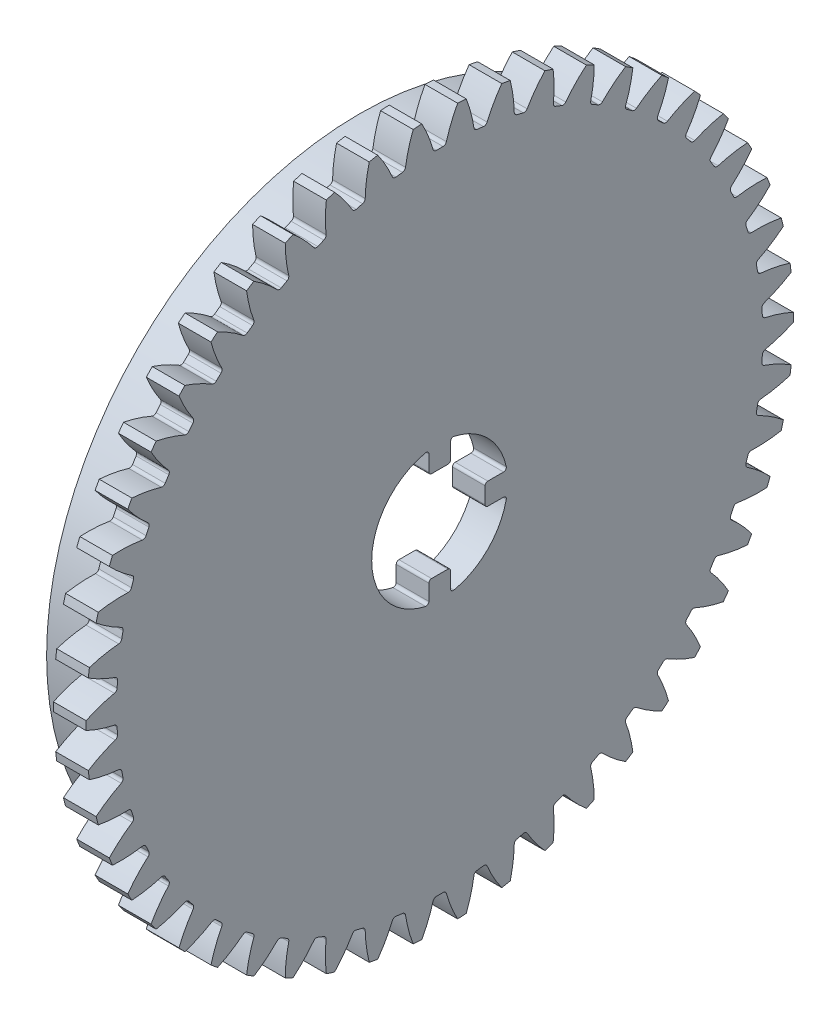
SolidWorks part; units mm, degrees
other "DifferReelC"
material "Nylon 101"
ref_plane "Plane1" through (0, 0, 0) normal (0, 0, 1) x (1, 0, 0)
ref_plane "Plane2" through (0, 0, 0) normal (0, 1, 0) x (1, 0, 0)
ref_plane "Plane3" through (0, 0, 0) normal (1, 0, 0) x (0, 0, -1)
sketch "BasProSke" plane through (0, 0, 0) normal (0, 1, 0) x (1, 0, 0)
  line L0 (-10, 0) -> (60, 0) construction
  line L1 (0, 0) -> (0, 13)
  line L2 (0, 0) -> (1.2, 0)
  line L3 (1.2, 0) -> (1.2, 13)
  line L4 (1.2, 13) -> (0, 13)
  dimension "Diameter" = 26
  dimension "Thickness" = 1.2
revolve "Base-Revolve" add sketch "BasProSke" angle 360 about L0
sketch "TooCutSke" plane through (0, 0, 0) normal (1, 0, 0) x (0, 0, -1)
  line L1 (0, 0) -> (0, 107) construction
  line L2 (0, 0) -> (-0.4259, 12.4927) construction
  line L3 (0, 0) -> (-1.5691, 24.9404) construction
  line L4 (-0.4259, 12.4927) -> (-0.7846, 12.4702) construction
  arc A0 (0.2187, 11.872) -> (-0.2187, 11.872) centre (0, 0) ccw
  arc A1 (0.6715, 13.0081) -> (-0.6715, 13.0081) centre (0, 0) ccw
  circle A2 centre (0, 0) radius 12.5 construction
  circle A3 centre (0, 0) radius 11.7462 construction
  arc A4 (-0.2187, 11.872) -> (-0.6715, 13.0081) centre (-5.0549, 10.6028) ccw
  arc A5 (0.6715, 13.0081) -> (0.2187, 11.872) centre (5.0549, 10.6028) ccw
  dimension "Root_dia" = 23.748
  dimension "Overcut_dia" = 26.0508
  dimension "Pitch_dia" = 25
  dimension "Base_dia" = 23.4923
  dimension "Flank_rad" = 5
  dimension "Half_ang" = 3.6
  dimension "Half_CT" = 0.3594
extrude "ToothCut" cut sketch "TooCutSke" along normal through all
fillet "RootFillets" radius 0.126 2 edges at (0.6, 11.872, -0.2187) (0.6, 11.872, 0.2187)
pattern_circular "TeethCuts" count 50 every 7.2 about axis through (-10, 0, 0) along (1, 0, 0) of "ToothCut", "RootFillets"
ref_plane "FarPln" through (1.2, 0, 0) normal (1, 0, 0) x (0, 0, -1)
sketch "BorSke" plane through (0, 0, 0) normal (1, 0, 0) x (0, 0, -1)
  circle A0 centre (0, 0) radius 2.5
  dimension "Diameter" = 5
extrude "Bore" cut sketch "BorSke" along normal mid plane 100.0001
sketch "PinSke" plane through (1.2, 0, 0) normal (1, 0, 0) x (0, 0, -1)
  line L0 (-0.4, 2.4678) -> (-0.4, 1.6678)
  line L1 (-0.4, 1.6678) -> (0.4, 1.6678)
  line L2 (0.4, 1.6678) -> (0.4, 2.4678)
  line L3 (50, 0) -> (-50, 0) construction
  line L4 (-0.4, -2.4678) -> (-0.4, -1.6678)
  line L5 (-0.4, -1.6678) -> (0.4, -1.6678)
  line L6 (0.4, -1.6678) -> (0.4, -2.4678)
  line L7 (2.4678, 0.4) -> (1.6678, 0.4)
  line L8 (1.6678, 0.4) -> (1.6678, -0.4)
  line L9 (1.6678, -0.4) -> (2.4678, -0.4)
  circle A0 centre (0, 0) radius 2.5 construction
  arc A1 (0.4, 2.4678) -> (-0.4, 2.4678) centre (0, 0) ccw
  arc A2 (0.4, -2.4678) -> (-0.4, -2.4678) centre (0, 0) cw
  arc A3 (2.4678, -0.4) -> (2.4678, 0.4) centre (0, 0) ccw
  point P21 (0, 0)
  dimension "D1" = 0.8
  dimension "D2" = 0.8
  dimension "D3" = 2
extrude "Pin" add sketch "PinSke" against normal up to surface (1.2 mm away) up to face at (0, 0, -2.5)
fillet "Fillet" radius 0.1 12 edges at (0.6, -1.6678, -0.4) (0.6, -1.6678, 0.4) (0.6, -2.4678, -0.4) (0.6, -2.4678, 0.4) (0.6, 1.6678, 0.4) (0.6, 1.6678, -0.4) (0.6, 2.4678, -0.4) (0.6, 2.4678, 0.4) (0.6, -0.4, -2.4678) (0.6, -0.4, -1.6678) (0.6, 0.4, -1.6678) (0.6, 0.4, -2.4678)
sketch "EdgeSke" plane through (0, 0, 0) normal (0, 0, 1) x (1, 0, 0)
  line L1 (-1.75, 10.5) -> (-1.75, 11.5)
  line L2 (-1.75, 11.5) -> (0, 11.5)
  line L3 (0, 11.5) -> (0, 10.5)
  line L4 (-1.75, 10.5) -> (0, 9.0316)
  line L5 (0, 9.0316) -> (0, 10.5)
  dimension "D1" = 1
  dimension "D2" = 11.5
  dimension "D3" = 1.75
  dimension "D4" = 50
revolve "Edge" add sketch "EdgeSke" angle 360 about L0
